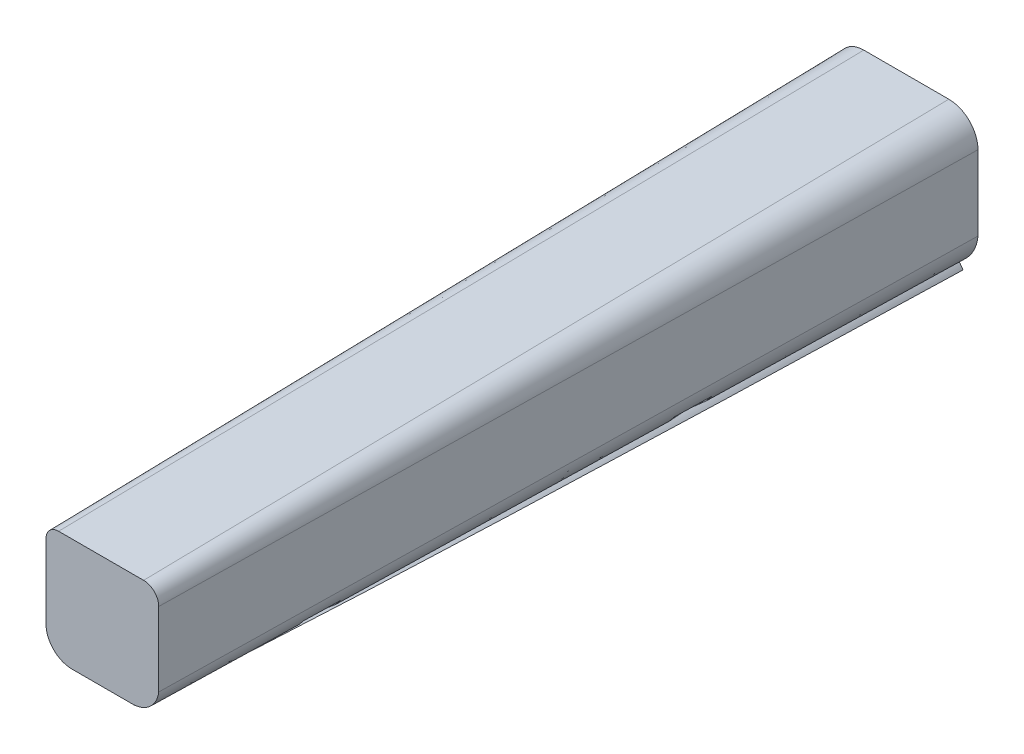
SolidWorks part; units mm, degrees
ref_plane "Front Plane" through (0, 0, 0) normal (0, 0, 1) x (1, 0, 0)
ref_plane "Top Plane" through (0, 0, 0) normal (0, 1, 0) x (1, 0, 0)
ref_plane "Right Plane" through (0, 0, 0) normal (1, 0, 0) x (0, 0, -1)
sketch "Sketch3" plane through (0, 0, 0) normal (0, 0, 1) x (1, 0, 0)
  line L1 (-35, 35) -> (35, 35)
  line L2 (-35, 35) -> (-35, -35)
  line L3 (-35, -35) -> (35, -35)
  line L4 (35, 35) -> (35, -35)
  line L5 (-35, 35) -> (35, -35) construction
  line L6 (-35, -35) -> (35, 35) construction
  point P0 (0, 0)
  dimension "D1" = 70
  dimension "D2" = 70
extrude "Boss-Extrude2" add sketch "Sketch3" along normal blind 500
sketch "Sketch5" plane through (0, 0, 500) normal (0, 0, 1) x (1, 0, 0)
  line L0 (-35, 35) -> (-35, -35) construction
  line L1 (35, 35) -> (-35, 35) construction
  arc A0 (-27.1754, 35) -> (-35, 27.1754) centre (-27.1754, 27.1754) ccw
  arc A1 (-35, 27.1754) -> (-46.4742, 47.1747) centre (-40.9044, 37.0791) cw
  arc A2 (-46.4742, 47.1747) -> (-27.1754, 35) centre (-42.7341, 31.7202) cw
  point P1 (-35, 26.4627)
  point P9 (-27.1754, 35)
extrude "Cut-Extrude1" cut sketch "Sketch5" against normal blind 500
sketch "Sketch6" plane through (0, 0, 500) normal (0, 0, 1) x (1, 0, 0)
  line L0 (35, 35) -> (-27.1754, 35) construction
  line L1 (35, -35) -> (35, 35) construction
  arc A0 (35, 25.618) -> (25.618, 35) centre (25.618, 25.618) ccw
  arc A1 (25.618, 35) -> (45.5676, 39.2002) centre (38.3834, 23.8453) cw
  arc A2 (45.5676, 39.2002) -> (35, 25.618) centre (41.6704, 31.3302) cw
  point P1 (45.6957, 39.2002)
  point P8 (26.4009, 35)
  point P11 (35, 25.618)
extrude "Cut-Extrude4" cut sketch "Sketch6" against normal blind 500
sketch "Sketch8" plane through (0, 0, 500) normal (0, 0, 1) x (1, 0, 0)
  line L0 (-35, 27.1754) -> (-35, -35) construction
  line L1 (-35, -35) -> (35, -35) construction
  arc A0 (-35, -18.8531) -> (-18.8531, -35) centre (-18.8531, -18.8531) ccw
  arc A1 (-35, -18.8531) -> (-57.0022, -25.7556) centre (-46.0011, -22.3043) ccw
  arc A2 (-57.0022, -25.7556) -> (-40.8479, -48.4964) centre (-37.5546, -29.0488) ccw
  arc A3 (-40.8479, -48.4964) -> (-18.8531, -35) centre (-27.249, -45.9878) ccw
  point P1 (-35, -23.9328)
  point P11 (-18.8531, -35)
extrude "Cut-Extrude5" cut sketch "Sketch8" against normal blind 500
sketch "Sketch9" plane through (0, 0, 500) normal (0, 0, 1) x (1, 0, 0)
  line L0 (-18.8531, -35) -> (35, -35) construction
  line L1 (35, -35) -> (35, 25.618) construction
  arc A0 (18.5755, -35) -> (35, -16.5793) centre (18.5755, -18.4674) ccw
  arc A1 (18.5755, -35) -> (36.4828, -51.2813) centre (19.5862, -51.8769) cw
  arc A2 (36.4828, -51.2813) -> (60.9006, -42.2477) centre (48.0169, -44.9404) ccw
  arc A3 (60.9006, -42.2477) -> (35, -16.5793) centre (40.9974, -36.4293) ccw
  point P1 (37.4537, -13.394)
  point P9 (18.5755, -35)
  point P12 (35, -16.5793)
  line M2 (-18.8531, -35) -> (35, -35)
  line M3 (35, -35) -> (35, 25.618)
extrude "Cut-Extrude9" cut sketch "Sketch9" against normal blind 500 contours A2 A3 A0 A1 M3 M2 | A0 A1 M2 M3 region at (31.3161, -31.4197, 500) region at (46.7642, -37.0099, 500)
draft "Draft1" type of draft neutral plane draft angle 1 faces to draft 8 face at (0.8719, -35, 250) face at (-28.5986, -28.5986, 250) face at (-31.8979, 31.8979, 250) face at (-0.7787, 35, 250) face at (-35, 4.1611, 250) face at (28.6168, -29.0657, 250) face at (31.2805, 31.2805, 250) face at (35, 2.6313, 250) neutral plane through (0, 0, 500) neutral plane normal (0, 0, 1) parameters "D1"=1
